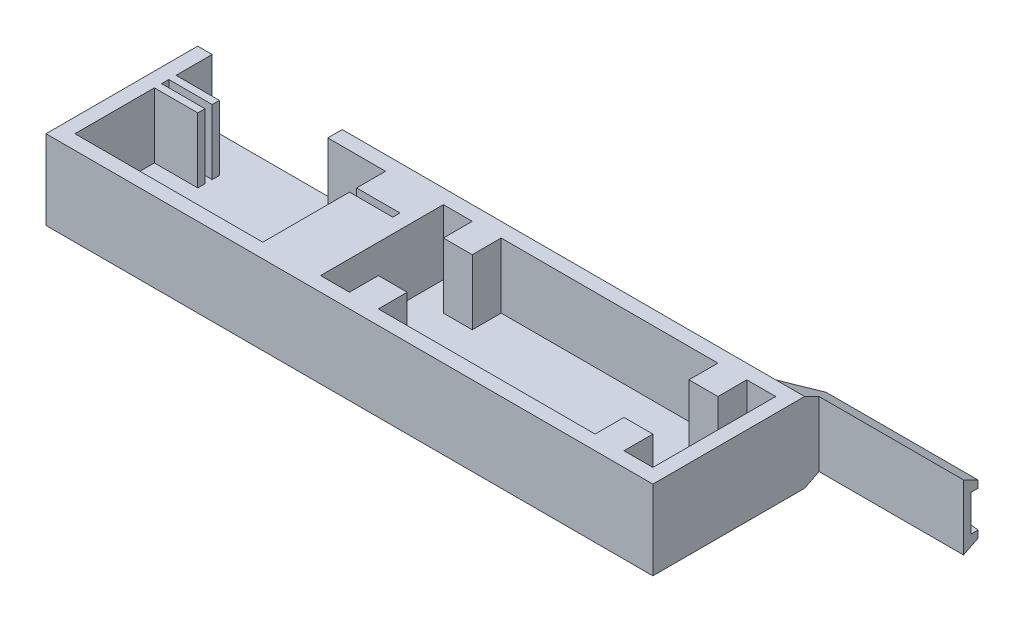
SolidWorks part; units mm, degrees
ref_plane "Front Plane" through (0, 0, 0) normal (0, 0, 1) x (1, 0, 0)
ref_plane "Top Plane" through (0, 0, 0) normal (0, 1, 0) x (1, 0, 0)
ref_plane "Right Plane" through (0, 0, 0) normal (1, 0, 0) x (0, 0, -1)
sketch "Sketch1" plane through (0, 0, 0) normal (0, 1, 0) x (1, 0, 0)
  line L0 (0, 0) -> (40, 0) construction
  line L1 (0, 0) -> (-40, 0) construction
  line L2 (40, -8.5) -> (40, 8.5)
  line L3 (40, 8.5) -> (-40, 8.5)
  line L4 (-40, 8.5) -> (-40, -8.5)
  line L5 (-40, -8.5) -> (40, -8.5)
  line L6 (40, 8.5) -> (40, 10.5) construction
  line L7 (40, 10.5) -> (42, 10.5) construction
  line L8 (-40, -8.5) -> (-40, -10.5) construction
  line L9 (-40, -10.5) -> (-42, -10.5) construction
  line L10 (-40, 0) -> (-34, 0) construction
  line L11 (-42, -10.5) -> (42, -10.5)
  line L12 (-42, -10.5) -> (-42, 10.5)
  line L13 (-42, 10.5) -> (42, 10.5)
  line L14 (42, -10.5) -> (42, 10.5)
  line L15 (-34, 0) -> (-14, 0) construction
  line L16 (-34, -8.5) -> (-34, 3.5)
  line L17 (-34, 3.5) -> (-40, 3.5)
  line L18 (-40, 3.5) -> (-40, 4.4487)
  line L19 (-34, 4.5) -> (-40, 4.5)
  line L20 (-34, 4.5) -> (-34, 8.5)
  line L21 (-14, 3.5) -> (-14, -8.5)
  line L22 (-14, 3.5) -> (-8, 3.5)
  line L23 (-8, 3.5) -> (-8, 4.5)
  line L24 (-8, 4.5) -> (-14, 4.5)
  line L25 (-14, 4.5) -> (-14, 8.5)
  line L26 (-8, 3.5) -> (-6, 3.5) construction
  line L27 (-6, 8.5) -> (-6, -8.5)
  line L28 (62, 12.5) -> (42, 12.5)
  line L29 (42, 12.5) -> (42, 10.5)
  line L30 (62, 14.5) -> (41, 14.5)
  line L31 (62, 13.5) -> (62, 12.5)
  line L32 (62, 12.5) -> (62, 14.5)
  line L33 (40, 10.5) -> (38, 10.5) construction
  line L34 (38, 10.5) -> (41, 14.5)
  point P7 (40, 0)
extrude "Boss-Extrude1" add sketch "Sketch1" along normal blind 2 contours L34 L13 L29 L28 L31 L32 L30 | L3 L27 L5 L2 | L27 L3 L25 L24 L23 L22 L21 L5 | L19 L20 L3 L4 | L24 L25 L3 L20 L19 L4 L17 L16 L5 L21 L22 L23 | L16 L17 L4 L5 | L11 L14 L13 L12 L5 L4 L3 L2 region at (17, 0, 0) region at (-9.9538, 0, 0.1846) region at (-24, 0, -0.1364) region at (-37, 0, 2.5) region at (-37, 0, -6.5) region at (-41.1341, 0, 0) region at (49.72, 0, -13.22)
extrude "Boss-Extrude2" add sketch "Sketch1<4>" along normal blind 11 contours L34 L13 L29 L28 L31 L32 L30 | L11 L14 L13 L12 L5 L4 L3 L2 | L27 L3 L25 L24 L23 L22 L21 L5 | L16 L17 L4 L5 | L19 L20 L3 L4 region at (-9.9538, 0, 0.1846) region at (-37, 0, 2.5) region at (-37, 0, -6.5) region at (-41.1341, 0, 0) region at (49.72, 0, -13.22)
sketch "Sketch1<4>" plane through (0, 0, 0) normal (0, 1, 0) x (1, 0, 0) same geometry as "Sketch1"
sketch "Sketch2" plane through (0, 11, 0) normal (0, 1, 0) x (1, 0, 0)
  line L1 (-40, 5.5) -> (-34, 5.5)
  line L2 (-34, 4.5) -> (-34, 8.5) construction
  line L3 (-34, 5.5) -> (-34, 8.5)
  line L4 (-34, 8.5) -> (-40, 8.5)
  line L5 (-40, 8.5) -> (-40, 5.5)
  line L6 (-40, 2.5) -> (-34, 2.5)
  line L7 (-34, -8.5) -> (-34, 3.5) construction
  line L8 (-34, 2.5) -> (-34, -8.5)
  line L9 (-34, -8.5) -> (-40, -8.5)
  line L10 (-40, -8.5) -> (-40, 2.5)
extrude "Cut-Extrude1" cut sketch "Sketch2" against normal blind 9
sketch "Sketch3" plane through (0, 0, -10.5) normal (0, 0, -1) x (-1, 0, 0)
  line L0 (42, 9) -> (40, 9) construction
  line L1 (42, 11) -> (42, 0) construction
  line L2 (40, 2) -> (22, 2)
  line L4 (40, 0) -> (40, 2) construction
  line L5 (42, 0) -> (-38, 0) construction
  line L6 (22, 2) -> (22, 11)
  line L7 (42, 11) -> (-38, 11) construction
  line L8 (22, 11) -> (40, 11)
  line L9 (40, 11) -> (40, 2)
extrude "Cut-Extrude2" cut sketch "Sketch3" against normal blind 2
sketch "Sketch4" plane through (0, 2, 0) normal (0, 1, 0) x (1, 0, 0)
  line L0 (-6, 8.5) -> (-2, 8.5) construction
  line L1 (40, 8.5) -> (-6, 8.5) construction
  line L2 (-2, 8.5) -> (-2, 4.5)
  line L3 (-2, 4.5) -> (2, 4.5)
  line L4 (2, 4.5) -> (2, 8.5)
  line L5 (-6, 8.5) -> (40, 8.5) construction
  line L6 (2, 8.5) -> (-2, 8.5)
  line L7 (-2, -8.5) -> (-2, -4.5)
  line L8 (40, -8.5) -> (-6, -8.5) construction
  line L9 (-2, -4.5) -> (2, -4.5)
  line L10 (2, -4.5) -> (2, -8.5)
  line L11 (-6, -8.5) -> (40, -8.5) construction
  line L12 (2, -8.5) -> (-2, -8.5)
  line L13 (40, 8.5) -> (36, 8.5) construction
  line L14 (36, 8.5) -> (36, 4.5)
  line L15 (36, 4.5) -> (32, 4.5)
  line L16 (32, 4.5) -> (32, 8.5)
  line L17 (32, 8.5) -> (36, 8.5)
  line L18 (36, -8.5) -> (36, -4.5)
  line L19 (36, -4.5) -> (32, -4.5)
  line L20 (32, -4.5) -> (32, -8.5)
  line L21 (32, -8.5) -> (36, -8.5)
extrude "Boss-Extrude3" add sketch "Sketch4" along normal blind 9 contours L6 L2 L3 L4 | L12 L7 L9 L10 | L21 L18 L19 L20 | L17 L14 L15 L16
sketch "Sketch5" plane through (0, 0, -14.5) normal (0, 0, -1) x (-1, 0, 0)
  line L0 (-62, 5.5) -> (-53.5, 5.5) construction
  line L1 (-62, 11) -> (-62, 0) construction
  line L2 (-62, 5.5) -> (-62, 8) construction
  line L3 (-62, 5.5) -> (-62, 8)
  line L4 (-62, 5.5) -> (-62, 3)
  line L5 (-62, 3) -> (-53.5, 4)
  line L6 (-53.5, 7) -> (-62, 8)
  line L7 (-53.5, 5.5) -> (-56, 5.5) construction
  line L8 (-62, 5.5) -> (-58.5, 5.5) construction
  line L9 (-62, 8) -> (-62, 9) construction
  circle A0 centre (-53.5, 5.5) radius 0.5
  circle A1 centre (-53.5, 5.5) radius 1.5
  circle A2 centre (-56, 5.5) radius 0.5
  circle A3 centre (-58.5, 5.5) radius 0.5
  line M5 (-62, 11) -> (-62, 0)
extrude "Cut-Extrude3" cut sketch "Sketch5" against normal blind 1 contours A1 L6 L5 A3 A2 M5 | A1 A0 region at (61.9014, 6.75, -14.5) region at (52.4693, 6.5307, -14.5)
sketch "Sketch6" plane through (62, 0, 0) normal (1, 0, 0) x (0, 0, -1)
  line L0 (14.5, 8) -> (14.5, 9) construction
  line L1 (14.5, 11) -> (14.5, 8) construction
  line L2 (14.5, 3) -> (14.5, 2) construction
  line L3 (14.5, 3) -> (14.5, 0) construction
  line L5 (14.5, 8.7106) -> (14.5, 11) construction
  line L6 (14.5, 11) -> (10.5, 11) construction
  line L7 (12.5, 11) -> (-10.5, 11) construction
  line L8 (10.5, 11) -> (14.5, 11)
  line L9 (14.5, 11) -> (14.5, 9)
  line L10 (14.5, 9) -> (10.5, 11)
  line L11 (14.5, 0) -> (10.5, 0) construction
  line L12 (12.5, 0) -> (-10.5, 0) construction
  line L13 (10.5, 0) -> (14.5, 2)
  line L14 (14.5, 2) -> (14.5, 0)
  line L15 (14.5, 0) -> (10.5, 0)
extrude "Cut-Extrude4" cut sketch "Sketch6" against normal blind 24 contours L10 L8 L9 | L15 L13 L14
